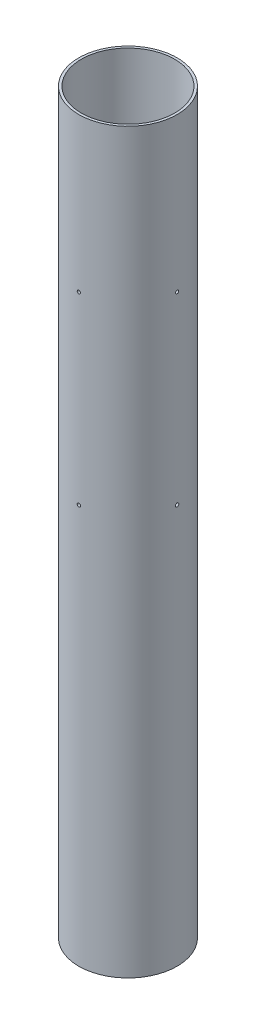
SolidWorks part; units mm, degrees
material "E-Glass Fiber"
ref_plane "Front Plane" through (0, 0, 0) normal (0, 0, 1) x (1, 0, 0)
ref_plane "Top Plane" through (0, 0, 0) normal (0, 1, 0) x (1, 0, 0)
ref_plane "Right Plane" through (0, 0, 0) normal (1, 0, 0) x (0, 0, -1)
sketch "Sketch1" plane through (0, 0, 0) normal (0, 1, 0) x (1, 0, 0)
  circle A0 centre (0, 0) radius 50.8
  dimension "D1" = 101.6
extrude "Coupler Extrusion" add sketch "Sketch1" along normal blind 762 thin thin type one direction reverse wall 2.54
ref_plane "Plane1" through (0, 0, 50.8) normal (0, 0, 1) x (1, 0, 0)
sketch "Sketch2" plane through (0, 0, 50.8) normal (0, 0, 1) x (1, 0, 0)
  line L0 (0, 762) -> (0, 0) construction
  line L1 (48.26, 762) -> (-48.26, 762) construction
  circle A0 centre (0, 603.25) radius 1.6383
  dimension "D1" = 3.2766
  dimension "D2" = 158.75
extrude "Bulkhead Hole" cut sketch "Sketch2" against normal up to next
pattern_circular "CirPattern1" count 4 over 360 about axis through (0, 762, 0) along (0, -1, 0) of "Bulkhead Hole"
sketch "Sketch3" plane through (0, 0, 50.8) normal (0, 0, 1) x (1, 0, 0)
  line L0 (0, 762) -> (0, 0) construction
  line L1 (50.8, 762) -> (-50.8, 762) construction
  line L2 (-48.26, 0) -> (48.26, 0) construction
  line L3 (-50.8, 0) -> (50.8, 0) construction
  line L4 (48.26, 762) -> (-48.26, 762) construction
  circle A0 centre (0, 412.75) radius 1.7526
  dimension "D1" = 3.5052
  dimension "D2" = 412.75
  dimension "D3" = 349.25
extrude "Lower Bulkhead Hole" cut sketch "Sketch3" against normal up to next
pattern_circular "CirPattern2" count 4 over 360 about axis through (0, 762, 0) along (0, -1, 0) of "Lower Bulkhead Hole" reverse direction yes
